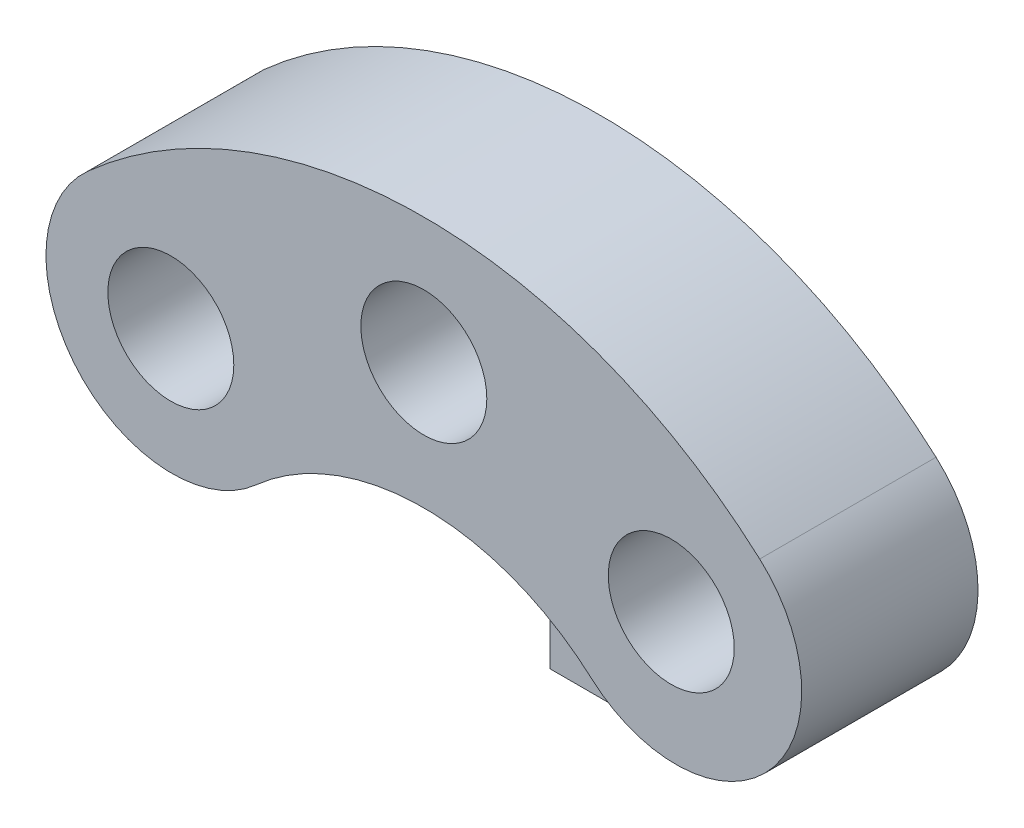
SolidWorks part; units mm, degrees
ref_plane "Front Plane" through (0, 0, 0) normal (0, 0, 1) x (1, 0, 0)
ref_plane "Top Plane" through (0, 0, 0) normal (0, 1, 0) x (1, 0, 0)
ref_plane "Right Plane" through (0, 0, 0) normal (1, 0, 0) x (0, 0, -1)
sketch "Sketch2" plane through (0, 0, 0) normal (0, 0, 1) x (1, 0, 0)
  arc A0 (-50, 55.9017) -> (50, 55.9017) centre (0, 0) cw construction
  arc A1 (66.6667, 74.5356) -> (-66.6667, 74.5356) centre (0, 0) ccw
  arc A2 (33.3333, 37.2678) -> (-33.3333, 37.2678) centre (0, 0) ccw
  arc A3 (33.3333, 37.2678) -> (66.6667, 74.5356) centre (50, 55.9017) ccw
  arc A4 (-66.6667, 74.5356) -> (-33.3333, 37.2678) centre (-50, 55.9017) ccw
  point P3 (0, 75)
  point P8 (0, 0)
  point P13 (0, 50)
  dimension "D1" = 50
  dimension "D2" = 100
  dimension "D3" = 50
extrude "Boss-Extrude1" add sketch "Sketch2" along normal blind 35
sketch "Sketch4" plane through (0, 0, 35) normal (0, 0, 1) x (1, 0, 0)
  circle A0 centre (-50.216, 55.7078) radius 12.5
  circle A1 centre (0, 75) radius 12.5
  circle A2 centre (49.1099, 56.6852) radius 12.5
  dimension "D1" = 75
  dimension "D2" = 75
  dimension "D3" = 75
extrude "Cut-Extrude1" cut sketch "Sketch4" against normal blind 25
sketch "Sketch12" plane through (0, 0, 0) normal (0, 0, -1) x (-1, 0, 0)
  line L1 (-10, 79.8504) -> (10, 79.8504)
  line L2 (-10, 79.8504) -> (-10, -0.1496)
  line L3 (-10, -0.1496) -> (10, -0.1496)
  line L4 (10, 79.8504) -> (10, -0.1496)
  dimension "D1" = 10
  dimension "D2" = 10
  dimension "D3" = 80
extrude "Boss-Extrude2" add sketch "Sketch12" along normal blind 10
sketch "Sketch13" plane through (0, 0, -10) normal (0, 0, -1) x (-1, 0, 0)
  circle A0 centre (0, 11.4794) radius 2
extrude "Cut-Extrude2" cut sketch "Sketch13" against normal through all
